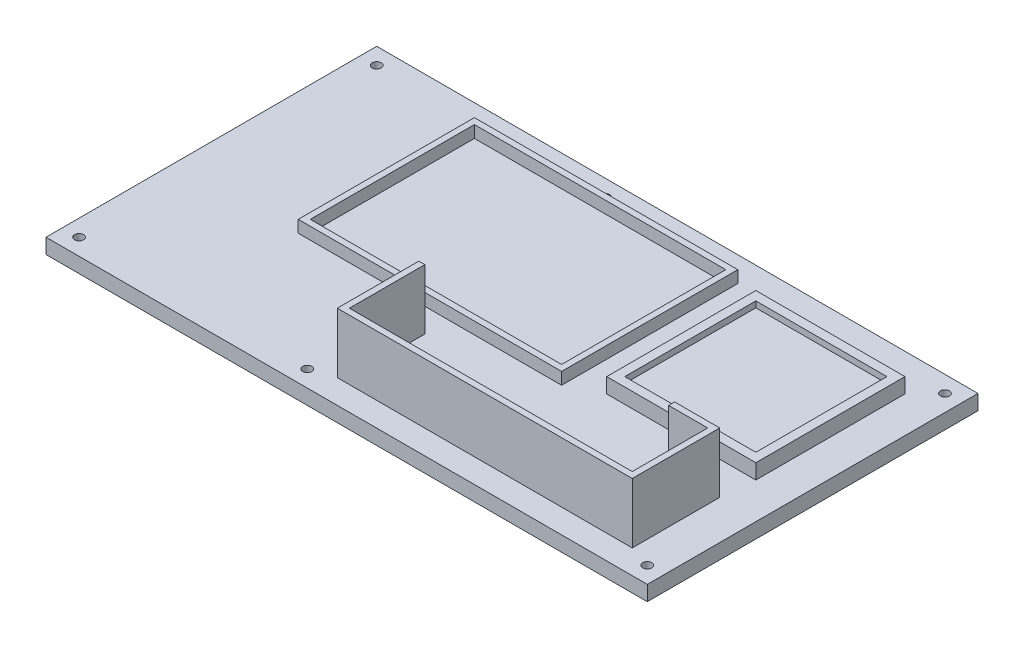
SolidWorks part; units mm, degrees
ref_plane "Front Plane" through (0, 0, 0) normal (0, 0, 1) x (1, 0, 0)
ref_plane "Top Plane" through (0, 0, 0) normal (0, 1, 0) x (1, 0, 0)
ref_plane "Right Plane" through (0, 0, 0) normal (1, 0, 0) x (0, 0, -1)
sketch "Sketch1" plane through (0, 0, 0) normal (0, 1, 0) x (1, 0, 0)
  line L1 (-100, -55) -> (100, -55)
  line L2 (-100, -55) -> (-100, 55)
  line L3 (-100, 55) -> (100, 55)
  line L4 (100, -55) -> (100, 55)
  line L5 (-100, -55) -> (100, 55) construction
  line L6 (-100, 55) -> (100, -55) construction
  point P0 (0, 0)
  dimension "D1" = 200
  dimension "D2" = 110
extrude "Boss-Extrude1" add sketch "Sketch1" along normal blind 5 contours L2 L1 L4 L3
sketch "Sketch4" plane through (0, 5, 0) normal (0, 1, 0) x (1, 0, 0)
  line L0 (100, -55) -> (100, 55) construction
  line L1 (-100, 55) -> (100, 55) construction
  line L2 (-100, -55) -> (-100, 55) construction
  line L3 (-100, -55) -> (100, -55) construction
  circle A0 centre (94.5, 49.5) radius 1.5
  circle A1 centre (-94.5, 49.5) radius 1.5
  circle A2 centre (-94.5, -49.5) radius 1.5
  circle A3 centre (94.5, -49.5) radius 1.5
  dimension "D3" = 3
  dimension "D6" = 3
  dimension "D9" = 3
  dimension "D12" = 3
  dimension "D1" = 5.5
  dimension "D2" = 5.5
  dimension "D4" = 5.5
  dimension "D5" = 5.5
  dimension "D7" = 5.5
  dimension "D8" = 5.5
  dimension "D10" = 5.5
  dimension "D11" = 5.5
extrude "Cut-Extrude1" cut sketch "Sketch4" against normal blind 10
sketch "Sketch5" plane through (0, 5, 0) normal (0, 1, 0) x (1, 0, 0)
  line L0 (100, -55) -> (100, 55) construction
  line L1 (85, -45) -> (-9.1, -45)
  line L2 (85, -45) -> (85, -19.9)
  line L3 (85, -19.9) -> (-9.1, -19.9)
  line L4 (-9.1, -45) -> (-9.1, -19.9)
  line L5 (-100, -55) -> (100, -55) construction
  line L6 (-9.1, -19.9) -> (-11.1, -19.9)
  line L7 (-11.1, -17.9) -> (87, -17.9)
  line L8 (-11.1, -17.9) -> (-11.1, -47)
  line L9 (-11.1, -47) -> (87, -47)
  line L10 (87, -17.9) -> (87, -47)
  line L12 (72, -19.9) -> (72, -17.9)
  dimension "D1" = 15
  dimension "D2" = 10
  dimension "D3" = 25.1
  dimension "D4" = 94.1
  dimension "D5" = 2
  dimension "D6" = 2
  dimension "D7" = 2
  dimension "D8" = 2
  dimension "D9" = 15
extrude "Boss-Extrude2" add sketch "Sketch5" along normal blind 20 contours L2 L1 L4 L6 L8 L9 L10 region at (86.0233, 5, 32.45)
sketch "Sketch7" plane through (0, 5, 0) normal (0, 1, 0) x (1, 0, 0)
  line L0 (100, -55) -> (100, 55) construction
  line L1 (41.4, 39.7) -> (85, 39.7)
  line L2 (41.4, 39.7) -> (41.4, -3.9)
  line L3 (41.4, -3.9) -> (85, -3.9)
  line L4 (85, 39.7) -> (85, -3.9)
  line L5 (72, -17.9) -> (87, -17.9) construction
  line L7 (38.4, 42.7) -> (88, 42.7)
  line L8 (38.4, 42.7) -> (38.4, -6.9)
  line L9 (38.4, -6.9) -> (88, -6.9)
  line L10 (88, 42.7) -> (88, -6.9)
  dimension "D1" = 43.6
  dimension "D2" = 43.6
  dimension "D3" = 15
  dimension "D4" = 14
  dimension "D5" = 3
  dimension "D6" = 3
  dimension "D7" = 3
  dimension "D8" = 3
extrude "Boss-Extrude3" add sketch "Sketch7" along normal blind 3 contours L2 L1 L4 L3
extrude "Boss-Extrude4" add sketch "Sketch7<3>" along normal blind 5
sketch "Sketch7<3>" plane through (0, 5, 0) normal (0, 1, 0) x (1, 0, 0) same geometry as "Sketch7"
sketch "Sketch8" plane through (0, 5, 0) normal (0, 1, 0) x (1, 0, 0)
  line L0 (41.4, 39.7) -> (41.4, -3.9) construction
  line L1 (-57.2, 44.7) -> (26.4, 44.7)
  line L2 (-57.2, 44.7) -> (-57.2, -9.9)
  line L3 (-57.2, -9.9) -> (26.4, -9.9)
  line L4 (26.4, 44.7) -> (26.4, -9.9)
  line L5 (-9.1, -19.9) -> (-11.1, -19.9) construction
  line L7 (-59.2, 46.7) -> (28.4, 46.7)
  line L8 (-59.2, 46.7) -> (-59.2, -11.9)
  line L9 (-59.2, -11.9) -> (28.4, -11.9)
  line L10 (28.4, 46.7) -> (28.4, -11.9)
  dimension "D1" = 15
  dimension "D2" = 54.6
  dimension "D3" = 83.6
  dimension "D4" = 10
  dimension "D5" = 2
  dimension "D6" = 2
  dimension "D7" = 2
  dimension "D8" = 2
extrude "Boss-Extrude5" add sketch "Sketch8" along normal blind 4
sketch "Sketch9" plane through (0, 5, 0) normal (0, 1, 0) x (1, 0, 0)
  line L0 (-11.1, -19.9) -> (-11.1, -47) construction
  line L1 (-100, -55) -> (100, -55) construction
  line L2 (-11.1, -19.9) -> (-11.1, -47) construction
  line L3 (-100, 55) -> (100, 55) construction
  circle A0 centre (-18.6, -49.5) radius 1.5
  circle A1 centre (-18.6, 49.5) radius 1.5
  dimension "D3" = 3
  dimension "D6" = 3
  dimension "D1" = 7.5
  dimension "D2" = 5.5
  dimension "D4" = 7.5
  dimension "D5" = 5.5
extrude "Cut-Extrude2" cut sketch "Sketch9" against normal blind 5
